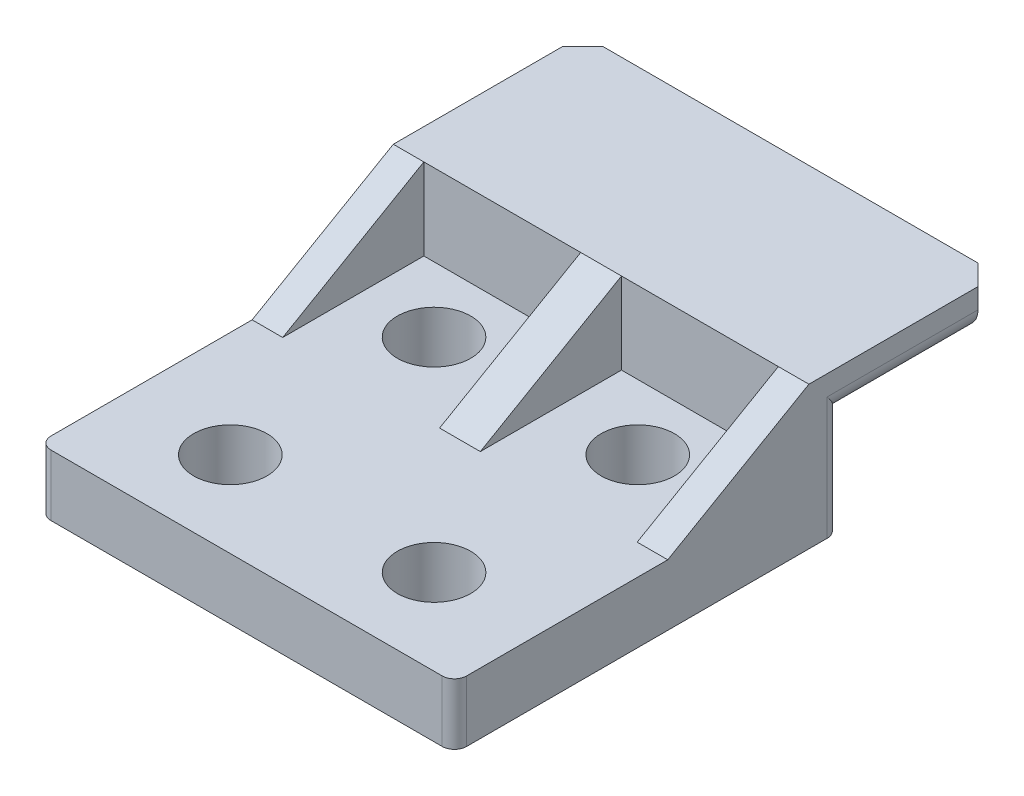
SolidWorks part; units mm, degrees
ref_plane "Front Plane" through (0, 0, 0) normal (0, 0, 1) x (1, 0, 0)
ref_plane "Top Plane" through (0, 0, 0) normal (0, 1, 0) x (1, 0, 0)
ref_plane "Right Plane" through (0, 0, 0) normal (1, 0, 0) x (0, 0, -1)
sketch "Sketch1" plane through (0, 0, 0) normal (0, 1, 0) x (1, 0, 0)
  line L1 (0, 0) -> (20.4, 0)
  line L2 (0, 0) -> (0, 18.9)
  line L3 (0, 18.9) -> (20.4, 18.9)
  line L4 (20.4, 0) -> (20.4, 18.9)
  dimension "D1" = 20.4
  dimension "D2" = 18.9
extrude "Boss-Extrude1" add sketch "Sketch1" along normal blind 3
sketch "Sketch2" plane through (0, 3, 0) normal (0, 1, 0) x (1, 0, 0)
  line L0 (10.2, 0) -> (10.2, 18.9) construction
  line L1 (0, 0) -> (20.4, 0) construction
  line L2 (20.4, 18.9) -> (0, 18.9) construction
  line L4 (5.2, 4.2) -> (5.2, 14.2) construction
  point P0 (5.2, 4.2)
  point P15 (5.2, 14.2)
  point P21 (15.2, 14.2)
  point P22 (15.2, 4.2)
  dimension "D1" = 5
  dimension "D2" = 10
  dimension "D3" = 4.2
hole_wizard "M3 Clearance Hole1" positions "Sketch2" profile "Sketch3" hole size "M3" standard "ANSI Metric" end condition through all
sketch "Sketch3" plane through (5.2, 3, -4.2) normal (1, 0, 0) x (0, 0, 1)
  line L0 (0, 0) -> (0, 3)
  line L1 (0, 3) -> (1.8, 3)
  line L2 (1.8, 3) -> (1.8, 0)
  line L5 (1.8, 0) -> (0, 0)
  line L11 (0, -6.35) -> (0, 107.95) construction
  dimension "Thru Hole Dia." = 3.6
  dimension "Thru Hole Depth" = 3
sketch "Sketch4" plane through (0, 0, -18.9) normal (0, 0, -1) x (-1, 0, 0)
  line L0 (-20.4, 3) -> (-20.4, 0) construction
  line L1 (0, 0) -> (-20.4, 0)
  line L2 (0, 0) -> (0, 2.4)
  line L3 (0, 2.4) -> (-20.4, 2.4)
  line L4 (-20.4, 0) -> (-20.4, 2.4)
  line L5 (-20.4, 3) -> (0, 3) construction
  line L6 (-20.4, 3) -> (0, 3) construction
  dimension "D1" = 2.4
extrude "Boss-Extrude2" add sketch "Sketch4" against normal blind 1.5
sketch "Sketch5" plane through (0, 3, 0) normal (0, 1, 0) x (1, 0, 0)
  line L1 (0, 17.4) -> (20.4, 17.4)
  line L2 (0, 17.4) -> (0, 26.7)
  line L3 (0, 26.7) -> (20.4, 26.7)
  line L4 (20.4, 17.4) -> (20.4, 26.7)
  line L6 (0, 18.9) -> (20.4, 18.9) construction
  line L7 (20.4, 18.9) -> (0, 18.9) construction
  line L8 (20.4, 0) -> (20.4, 18.9) construction
  line L9 (0, 18.9) -> (0, 0) construction
  point P11 (0, 0)
  point P12 (-0.211, 21.9)
  point P13 (0, 21.9)
  point P16 (0, 0)
  point P17 (0, 18.6175)
  point P18 (0, 19.4731)
  dimension "D1" = 7.8
  dimension "D2" = 1.5
extrude "Boss-Extrude3" add sketch "Sketch5" along normal blind 4 and the other way offset from surface 2.9 other way up to face at (10.2, 0, -9.45)
chamfer "Chamfer1" distance 3.6 distance2 2.6 2 edges at (20.4, 2.9, -22.8) (0, 2.9, -22.8) first distance on face at (10.2, 2.9, -22.8)
fillet "Fillet2" radius 1 4 edges at (16.8, 2.9, -22.8) (3.6, 2.9, -22.8) (0, 5.5, -22.8) (20.4, 5.5, -22.8)
chamfer "Chamfer2" [suppressed] distance 3 distance2 1.5
chamfer "Chamfer3" distance 1 angle 45 9 edges at (20.4, 6.5057, -26.7) (0, 6.5057, -26.7) (20.2904, 5.5561, -26.7) (0.1096, 5.5561, -26.7) (18.5238, 4.145, -26.7) (16.7843, 2.9485, -26.7) (1.8762, 4.145, -26.7) (3.6157, 2.9485, -26.7) (10.2, 2.9, -26.7)
fillet "Fillet1" radius 0.6 4 edges at (0, 1.5, 0) (20.4, 1.5, 0) (20.4, 3.0057, -18.9) (0, 3.0057, -18.9)
sketch "Sketch6" plane through (0, 3, 0) normal (0, 1, 0) x (1, 0, 0)
  line L0 (10.2, 17.4) -> (10.2, 0) construction
  line L1 (6.7877, 11.45) -> (8.3754, 14.2)
  line L2 (8.3754, 14.2) -> (6.7877, 16.95)
  line L3 (6.7877, 16.95) -> (3.6123, 16.95)
  line L4 (3.6123, 16.95) -> (2.0246, 14.2)
  line L5 (2.0246, 14.2) -> (3.6123, 11.45)
  line L6 (3.6123, 11.45) -> (6.7877, 11.45)
  line L7 (0, 17.4) -> (20.4, 17.4) construction
  line L8 (0.6, 0) -> (19.8, 0) construction
  line L9 (16.7877, 11.45) -> (13.6123, 11.45)
  line L10 (18.3754, 14.2) -> (16.7877, 11.45)
  line L11 (16.7877, 16.95) -> (18.3754, 14.2)
  line L12 (13.6123, 16.95) -> (16.7877, 16.95)
  line L13 (12.0246, 14.2) -> (13.6123, 16.95)
  line L14 (13.6123, 11.45) -> (12.0246, 14.2)
  circle A0 centre (5.2, 14.2) radius 2.75 construction
  point P15 (9.2, 0)
  dimension "D1" = 5.5
ref_plane "Plane1" through (10.2, 0, 0) normal (-1, 0, 0) x (0, 0, 1)
sketch "Sketch7" plane through (10.2, 0, 0) normal (-1, 0, 0) x (0, 0, 1)
  line L0 (-17.4, 7) -> (-10.4718, 3)
  line L1 (-17.4, 3) -> (0, 3) construction
  line L2 (-14.2, 3) -> (-11.45, 3) construction
  dimension "D1" = 30
rib "Rib1" sketch "Sketch7" sketch "Sketch7" thickness 2 extrusion direction parallel to sketch draft on no parameters "D1"=2
sketch "Sketch8" plane through (0, 0, 0) normal (-1, 0, 0) x (0, 0, 1)
  line L0 (-17.4, 7) -> (-10.4718, 3) construction
  line L1 (-17.4, 7) -> (-10.4718, 3)
rib "Rib2" sketch "Sketch8" sketch "Sketch8" thickness 1.5 extrusion direction parallel to sketch draft on no parameters "D1"=1.5
sketch "Sketch9" plane through (20.4, 0, 0) normal (1, 0, 0) x (0, 0, -1)
  line L0 (17.4, 7) -> (10.4718, 3) construction
  line L1 (17.4, 7) -> (10.4718, 3)
rib "Rib10" sketch "Sketch9" sketch "Sketch9" thickness 1.5 extrusion direction parallel to sketch draft on no parameters "D1"=1.5
